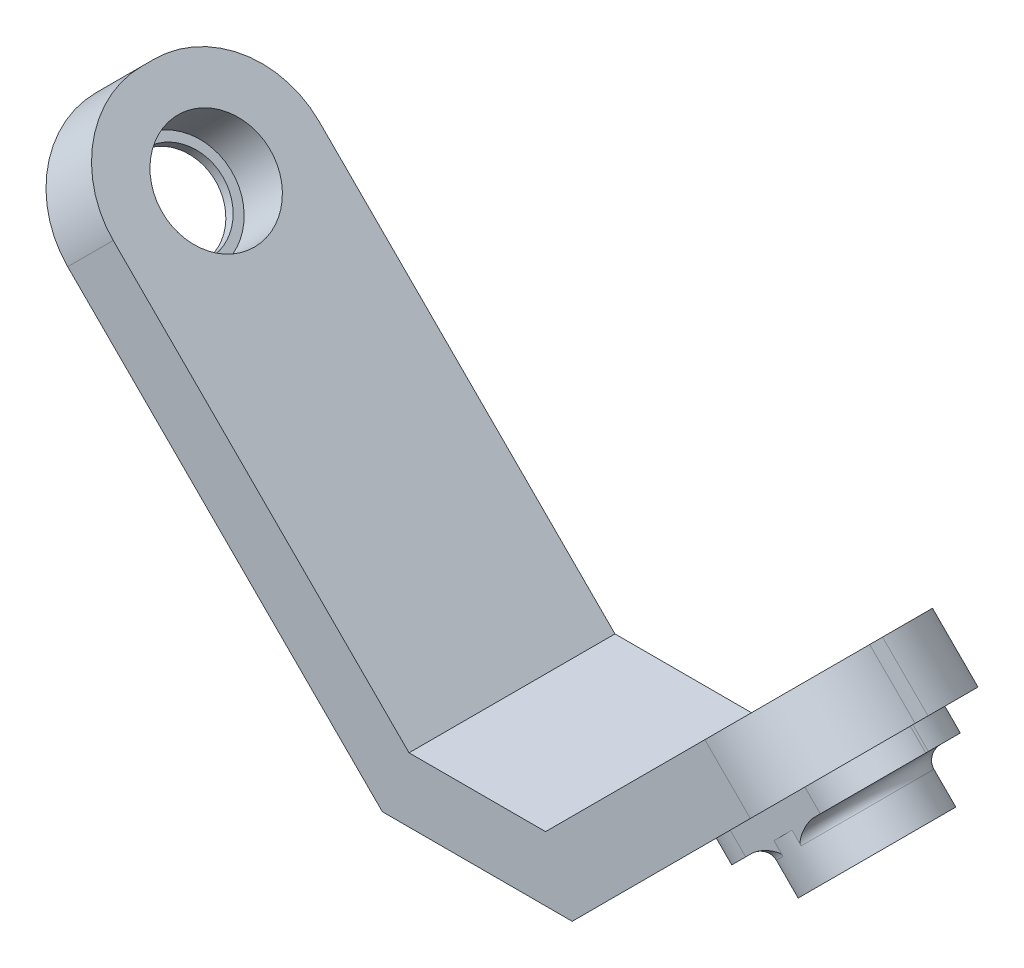
SolidWorks part; units mm, degrees
ref_plane "正面" through (0, 0, 0) normal (0, 0, 1) x (1, 0, 0)
ref_plane "平面" through (0, 0, 0) normal (0, 1, 0) x (1, 0, 0)
ref_plane "右側面" through (0, 0, 0) normal (1, 0, 0) x (0, 0, -1)
sketch "ｽｹｯﾁ1" plane through (0, 0, 0) normal (0, 0, 1) x (1, 0, 0)
  line L0 (0, 0) -> (-29.7487, 29.7487)
  line L1 (-29.7487, 29.7487) -> (-26.2132, 33.2843)
  line L2 (-26.2132, 33.2843) -> (2.0711, 5)
  line L3 (2.0711, 5) -> (12.6777, 5)
  line L4 (12.6777, 5) -> (30.3553, 22.6777)
  line L5 (30.3553, 22.6777) -> (33.8909, 19.1421)
  line L6 (33.8909, 19.1421) -> (14.7487, 0)
  line L7 (14.7487, 0) -> (0, 0)
  point P6 (21.5165, 13.8388)
  point P10 (-20.9099, 27.981)
  dimension "D1" = 135
  dimension "D2" = 135
  dimension "D3" = 5
  dimension "D4" = 5
  dimension "D5" = 5
  dimension "D6" = 7.5
  dimension "D7" = 45
  dimension "D9" = 25
  dimension "D8" = 25
extrude "ﾎﾞｽ - 押し出し1" add sketch "ｽｹｯﾁ1" along normal mid plane 16
fillet "ﾌｨﾚｯﾄ1" radius 7.5 4 edges at (32.1231, 20.9099, -8) (32.1231, 20.9099, 8) (-27.981, 31.5165, -8) (-27.981, 31.5165, 8)
sketch "ｽｹｯﾁ2" plane through (0, 0, 0) normal (-0.7071, -0.7071, 0) x (0, 0, 1)
  line L1 (0.5, 42.0711) -> (-0.5, 42.0711) construction
  circle A0 centre (0, 34.5711) radius 4.2
  dimension "D1" = 8.4
  dimension "D2" = 7.5
extrude "ｶｯﾄ - 押し出し1" cut sketch "ｽｹｯﾁ2" along normal blind 4.2 from surface starting at face at (-15.3835, 22.4545, 0)
sketch "ｽｹｯﾁ3" plane through (7.3744, -7.3744, 0) normal (0.7071, -0.7071, 0) x (0, 0, -1)
  line L0 (-0.5, 37.5) -> (0.5, 37.5) construction
  line L1 (-6.5, 21) -> (6.5, 21) construction
  line L2 (6.5, 21) -> (6.5, 34) construction
  line L3 (6.5, 34) -> (-6.5, 34) construction
  line L4 (-6.5, 34) -> (-6.5, 21) construction
  line L6 (0.1, 36.5) -> (-0.1, 36.5)
  line L7 (5, 31.6) -> (5, 23.4)
  line L8 (0.1, 18.5) -> (-0.1, 18.5)
  line L9 (-5, 31.6) -> (-5, 23.4)
  line L10 (5, 36.5) -> (-5, 18.5) construction
  line L11 (5, 18.5) -> (-5, 36.5) construction
  circle A0 centre (0, 27.5) radius 6.5 construction
  arc A1 (0.1, 36.5) -> (5, 31.6) centre (0.1, 31.6) cw
  arc A2 (5, 23.4) -> (0.1, 18.5) centre (0.1, 23.4) cw
  arc A3 (-0.1, 36.5) -> (-5, 31.6) centre (-0.1, 31.6) ccw
  arc A4 (-0.1, 18.5) -> (-5, 23.4) centre (-0.1, 23.4) cw
  point P7 (0, 37.5)
  dimension "D2" = 13
  dimension "D5" = 4.9
  dimension "D1" = 10
  dimension "D3" = 10
  dimension "D4" = 18
extrude "ｶｯﾄ - 押し出し2" cut sketch "ｽｹｯﾁ3" against normal blind 2.5
sketch "ｽｹｯﾁ5" plane through (5.6066, -5.6066, 0) normal (0.7071, -0.7071, 0) x (0, 0, -1)
  line L0 (-0.5, 37.5) -> (0.5, 37.5) construction
  circle A0 centre (0, 27.5) radius 1.9
  point P5 (0, 37.5)
  dimension "D2" = 3.8
  dimension "D1" = 10
extrude "ｶｯﾄ - 押し出し5" cut sketch "ｽｹｯﾁ5" against normal through all
sketch "ｽｹｯﾁ6" plane through (5.6066, -5.6066, 0) normal (0.7071, -0.7071, 0) x (0, 0, -1)
  line L0 (-0.1, 36.4) -> (0.1, 36.4)
  line L6 (-4.9, 31.6) -> (-4.9, 23.4)
  line L7 (-4.9, 31.6) -> (-4.9, 23.4)
  line L8 (-0.1, 18.6) -> (0.1, 18.6)
  line L9 (-0.1, 18.6) -> (0.1, 18.6)
  line L10 (4.9, 23.4) -> (4.9, 31.6)
  line L16 (4.9, 23.4) -> (4.9, 31.6)
  line L18 (0.1, 36.4) -> (-0.1, 36.4)
  circle A0 centre (0, 27.5) radius 1.9 construction
  circle A1 centre (0, 27.5) radius 1.9
  arc A6 (-0.1, 36.4) -> (-4.9, 31.6) centre (-0.1, 31.6) ccw
  arc A7 (-0.1, 36.4) -> (-4.9, 31.6) centre (-0.1, 31.6) ccw
  arc A8 (-4.9, 23.4) -> (-0.1, 18.6) centre (-0.1, 23.4) ccw
  arc A9 (-4.9, 23.4) -> (-0.1, 18.6) centre (-0.1, 23.4) ccw
  arc A10 (0.1, 18.6) -> (4.9, 23.4) centre (0.1, 23.4) ccw
  arc A11 (0.1, 18.6) -> (4.9, 23.4) centre (0.1, 23.4) ccw
  arc A12 (4.9, 31.6) -> (0.1, 36.4) centre (0.1, 31.6) ccw
  arc A13 (4.9, 31.6) -> (0.1, 36.4) centre (0.1, 31.6) ccw
  dimension "D1" = 0.1
extrude "ﾎﾞｽ - 押し出し2" add sketch "ｽｹｯﾁ6" along normal blind 4 from offset 0.2 separate body
sketch "ｽｹｯﾁ12" plane through (8.5765, -8.5765, 0) normal (0.7071, -0.7071, 0) x (0, 0, -1)
  circle A0 centre (0, 27.5) radius 5
  dimension "D1" = 10
extrude "ﾎﾞｽ - 押し出し3" add sketch "ｽｹｯﾁ12" along normal blind 3.4
sketch "ｽｹｯﾁ7" plane through (10.9806, -10.9806, 0) normal (0.7071, -0.7071, 0) x (0, 0, -1)
  line L0 (-2.6375, 27.1375) -> (-3, 27.5) construction
  line L1 (-3, 27.5) -> (-2.6375, 27.8625) construction
  line L2 (0, 27.5) -> (-2.6375, 27.1375) construction
  line L3 (0, 27.5) -> (-2.6375, 27.8625) construction
  line L4 (0, 27.5) -> (-3, 27.5) construction
  line L5 (-2.6375, 27.1375) -> (-2.95, 27.45)
  line L6 (-2.95, 27.45) -> (-3.95, 27.45)
  line L7 (-2.95, 27.45) -> (-2.95, 27.55) construction
  line L8 (-2.95, 27.55) -> (-3.95, 27.55)
  line L9 (-3.95, 27.45) -> (-3.95, 27.55)
  line L10 (-2.95, 27.55) -> (-2.6375, 27.8625)
  line L11 (-2.6375, 27.8625) -> (-2.8541, 28.2478)
  line L12 (-2.8541, 28.2478) -> (-3.817, 28.5176)
  line L13 (-2.8271, 28.344) -> (-3.79, 28.6138)
  line L14 (-3.817, 28.5176) -> (-3.79, 28.6138)
  line L15 (-2.8271, 28.344) -> (-2.4419, 28.5607)
  line L16 (-2.4419, 28.5607) -> (-2.5465, 28.9901)
  line L17 (-2.5465, 28.9901) -> (-3.4009, 29.5096)
  line L18 (-2.4946, 29.0755) -> (-3.349, 29.5951)
  line L19 (-3.4009, 29.5096) -> (-3.349, 29.5951)
  line L20 (-2.4946, 29.0755) -> (-2.0652, 29.1801)
  line L21 (-2.0652, 29.1801) -> (-2.0501, 29.6218)
  line L22 (-2.0501, 29.6218) -> (-2.7326, 30.3527)
  line L23 (-1.977, 29.6901) -> (-2.6595, 30.4209)
  line L24 (-2.7326, 30.3527) -> (-2.6595, 30.4209)
  line L25 (-1.977, 29.6901) -> (-1.5353, 29.675)
  line L26 (-1.5353, 29.675) -> (-1.4016, 30.0963)
  line L27 (-1.4016, 30.0963) -> (-1.8617, 30.9841)
  line L28 (-1.3128, 30.1423) -> (-1.7729, 31.0301)
  line L29 (-1.8617, 30.9841) -> (-1.7729, 31.0301)
  line L30 (-1.3128, 30.1423) -> (-0.8915, 30.0086)
  line L31 (-0.8915, 30.0086) -> (-0.6491, 30.3781)
  line L32 (-0.6491, 30.3781) -> (-0.8526, 31.3572)
  line L33 (-0.5512, 30.3985) -> (-0.7547, 31.3776)
  line L34 (-0.8526, 31.3572) -> (-0.7547, 31.3776)
  line L35 (-0.5512, 30.3985) -> (-0.1817, 30.1561)
  line L36 (-0.1817, 30.1561) -> (0.1514, 30.4465)
  line L37 (0.1514, 30.4465) -> (0.2197, 31.4442)
  line L38 (0.2512, 30.4397) -> (0.3194, 31.4374)
  line L39 (0.2197, 31.4442) -> (0.3194, 31.4374)
  line L40 (0.2512, 30.4397) -> (0.5417, 30.1066)
  line L41 (0.5417, 30.1066) -> (0.9408, 30.2964)
  line L42 (0.9408, 30.2964) -> (1.2757, 31.2387)
  line L43 (1.035, 30.2629) -> (1.3699, 31.2052)
  line L44 (1.2757, 31.2387) -> (1.3699, 31.2052)
  line L45 (1.035, 30.2629) -> (1.2248, 29.8638)
  line L46 (1.2248, 29.8638) -> (1.6604, 29.9389)
  line L47 (1.6604, 29.9389) -> (2.237, 30.7559)
  line L48 (1.7421, 29.8812) -> (2.3187, 30.6982)
  line L49 (2.237, 30.7559) -> (2.3187, 30.6982)
  line L50 (1.7421, 29.8812) -> (1.8171, 29.4457)
  line L51 (1.8171, 29.4457) -> (2.2568, 29.4005)
  line L52 (2.2568, 29.4005) -> (3.0325, 30.0316)
  line L53 (2.3199, 29.3229) -> (3.0956, 29.954)
  line L54 (3.0325, 30.0316) -> (3.0956, 29.954)
  line L55 (2.3199, 29.3229) -> (2.2747, 28.8833)
  line L56 (2.2747, 28.8833) -> (2.6859, 28.7211)
  line L57 (2.6859, 28.7211) -> (3.6031, 29.1195)
  line L58 (2.7257, 28.6294) -> (3.6429, 29.0278)
  line L59 (3.6031, 29.1195) -> (3.6429, 29.0278)
  line L60 (2.7257, 28.6294) -> (2.5636, 28.2183)
  line L61 (2.5636, 28.2183) -> (2.9157, 27.9512)
  line L62 (2.9157, 27.9512) -> (3.9064, 28.0874)
  line L63 (2.9293, 27.8522) -> (3.92, 27.9883)
  line L64 (3.9064, 28.0874) -> (3.92, 27.9883)
  line L65 (2.9293, 27.8522) -> (2.6623, 27.5)
  line L66 (2.6623, 27.5) -> (2.9293, 27.1478)
  line L67 (2.9293, 27.1478) -> (3.92, 27.0117)
  line L68 (2.9157, 27.0488) -> (3.9064, 26.9126)
  line L69 (3.92, 27.0117) -> (3.9064, 26.9126)
  line L70 (2.9157, 27.0488) -> (2.5636, 26.7817)
  line L71 (2.5636, 26.7817) -> (2.7257, 26.3706)
  line L72 (2.7257, 26.3706) -> (3.6429, 25.9722)
  line L73 (2.6859, 26.2789) -> (3.6031, 25.8805)
  line L74 (3.6429, 25.9722) -> (3.6031, 25.8805)
  line L75 (2.6859, 26.2789) -> (2.2747, 26.1167)
  line L76 (2.2747, 26.1167) -> (2.3199, 25.6771)
  line L77 (2.3199, 25.6771) -> (3.0956, 25.046)
  line L78 (2.2568, 25.5995) -> (3.0325, 24.9684)
  line L79 (3.0956, 25.046) -> (3.0325, 24.9684)
  line L80 (2.2568, 25.5995) -> (1.8171, 25.5543)
  line L81 (1.8171, 25.5543) -> (1.7421, 25.1188)
  line L82 (1.7421, 25.1188) -> (2.3187, 24.3018)
  line L83 (1.6604, 25.0611) -> (2.237, 24.2441)
  line L84 (2.3187, 24.3018) -> (2.237, 24.2441)
  line L85 (1.6604, 25.0611) -> (1.2248, 25.1362)
  line L86 (1.2248, 25.1362) -> (1.035, 24.7371)
  line L87 (1.035, 24.7371) -> (1.3699, 23.7948)
  line L88 (0.9408, 24.7036) -> (1.2757, 23.7613)
  line L89 (1.3699, 23.7948) -> (1.2757, 23.7613)
  line L90 (0.9408, 24.7036) -> (0.5417, 24.8934)
  line L91 (0.5417, 24.8934) -> (0.2512, 24.5603)
  line L92 (0.2512, 24.5603) -> (0.3194, 23.5626)
  line L93 (0.1514, 24.5535) -> (0.2197, 23.5558)
  line L94 (0.3194, 23.5626) -> (0.2197, 23.5558)
  line L95 (0.1514, 24.5535) -> (-0.1817, 24.8439)
  line L96 (-0.1817, 24.8439) -> (-0.5512, 24.6015)
  line L97 (-0.5512, 24.6015) -> (-0.7547, 23.6224)
  line L98 (-0.6491, 24.6219) -> (-0.8526, 23.6428)
  line L99 (-0.7547, 23.6224) -> (-0.8526, 23.6428)
  line L100 (-0.6491, 24.6219) -> (-0.8915, 24.9914)
  line L101 (-0.8915, 24.9914) -> (-1.3128, 24.8577)
  line L102 (-1.3128, 24.8577) -> (-1.7729, 23.9699)
  line L103 (-1.4016, 24.9037) -> (-1.8617, 24.0159)
  line L104 (-1.7729, 23.9699) -> (-1.8617, 24.0159)
  line L105 (-1.4016, 24.9037) -> (-1.5353, 25.325)
  line L106 (-1.5353, 25.325) -> (-1.977, 25.3099)
  line L107 (-1.977, 25.3099) -> (-2.6595, 24.5791)
  line L108 (-2.0501, 25.3782) -> (-2.7326, 24.6473)
  line L109 (-2.6595, 24.5791) -> (-2.7326, 24.6473)
  line L110 (-2.0501, 25.3782) -> (-2.0652, 25.8199)
  line L111 (-2.0652, 25.8199) -> (-2.4946, 25.9245)
  line L112 (-2.4946, 25.9245) -> (-3.349, 25.4049)
  line L113 (-2.5465, 26.0099) -> (-3.4009, 25.4904)
  line L114 (-3.349, 25.4049) -> (-3.4009, 25.4904)
  line L115 (-2.5465, 26.0099) -> (-2.4419, 26.4393)
  line L116 (-2.4419, 26.4393) -> (-2.8271, 26.656)
  line L117 (-2.8271, 26.656) -> (-3.79, 26.3862)
  line L118 (-2.8541, 26.7522) -> (-3.817, 26.4824)
  line L119 (-3.79, 26.3862) -> (-3.817, 26.4824)
  line L120 (-2.8541, 26.7522) -> (-2.6375, 27.1375)
  circle A0 centre (0, 27.5) radius 3 construction
  circle A1 centre (0, 27.5) radius 2.6623 construction
  point P147 (0, 27.5)
  dimension "D1" = 6
  dimension "D2" = 7.826
  dimension "D3" = 7.826
  dimension "D4" = 0.1
  dimension "D5" = 1
  dimension "D6" = 23
extrude "ｶｯﾄ - 押し出し6" cut sketch "ｽｹｯﾁ7" against normal blind 3.4
sketch "ｽｹｯﾁ9" plane through (8.5765, -8.5765, 0) normal (0.7071, -0.7071, 0) x (0, 0, -1)
  circle A0 centre (0, 20.5) radius 1.4
  circle A1 centre (0, 34.5) radius 1.4
  circle A3 centre (0, 27.5) radius 1.9 construction
  dimension "D1" = 2.8
  dimension "D3" = 7
  dimension "D2" = 14
extrude "ｶｯﾄ - 押し出し7" cut sketch "ｽｹｯﾁ9" against normal through all
sketch "ｽｹｯﾁ10" plane through (8.5765, -8.5765, 0) normal (0.7071, -0.7071, 0) x (0, 0, -1)
  line L19 (-0.75, 20.5) -> (-0.375, 19.8505)
  line L20 (-0.375, 19.8505) -> (0.375, 19.8505)
  line L21 (0.375, 19.8505) -> (0.75, 20.5)
  line L22 (0.75, 20.5) -> (0.375, 21.1495)
  line L23 (0.375, 21.1495) -> (-0.375, 21.1495)
  line L24 (-0.375, 21.1495) -> (-0.75, 20.5)
  line L25 (-0.75, 34.5) -> (-0.375, 33.8505)
  line L26 (-0.375, 33.8505) -> (0.375, 33.8505)
  line L27 (0.375, 33.8505) -> (0.75, 34.5)
  line L28 (0.75, 34.5) -> (0.375, 35.1495)
  line L29 (0.375, 35.1495) -> (-0.375, 35.1495)
  line L30 (-0.375, 35.1495) -> (-0.75, 34.5)
  circle A0 centre (0, 20.5) radius 0.6495 construction
  circle A1 centre (0, 34.5) radius 1.4
  circle A3 centre (0, 34.5) radius 1.4 construction
  circle A5 centre (0, 20.5) radius 1.4
  circle A7 centre (0, 20.5) radius 1.4 construction
  circle A8 centre (0, 34.5) radius 0.6495 construction
  dimension "D3" = 1.5
  dimension "D1" = 0
  dimension "D2" = 0
extrude "ｶｯﾄ - 押し出し8" cut sketch "ｽｹｯﾁ10" against normal through all
sketch "ｽｹｯﾁ11" plane through (0.5657, 0.5657, 0) normal (-0.7071, -0.7071, 0) x (0, 0, 1)
  circle A0 centre (0, 34.5711) radius 3.5
  dimension "D1" = 7
extrude "ｶｯﾄ - 押し出し9" cut sketch "ｽｹｯﾁ11" along normal blind 10
fillet "ﾌｨﾚｯﾄ2" radius 1 2 edges at (24.4864, 7.3335, 0) (31.5574, 14.4045, 0)
sketch "ｽｹｯﾁ13" plane through (3.8388, -3.8388, 0) normal (-0.7071, 0.7071, 0) x (0, 0, 1)
  circle A0 centre (0, 34.5) radius 2.4
  circle A1 centre (0, 20.5) radius 2.4
  dimension "D1" = 4.8
extrude "ｶｯﾄ - 押し出し10" cut sketch "ｽｹｯﾁ13" against normal blind 1.2 draft 45
equation "\"D4@ｽｹｯﾁ1\"=\"D3@ｽｹｯﾁ1\""
equation "\"D5@ｽｹｯﾁ1\"=\"D3@ｽｹｯﾁ1\""
equation "\"D2@ｽｹｯﾁ7\"=360deg/46"
equation "\"D3@ｽｹｯﾁ7\"=\"D2@ｽｹｯﾁ7\""
equation "\"D2@ｽｹｯﾁ9\"=\"D3@ｽｹｯﾁ9\"*2"
